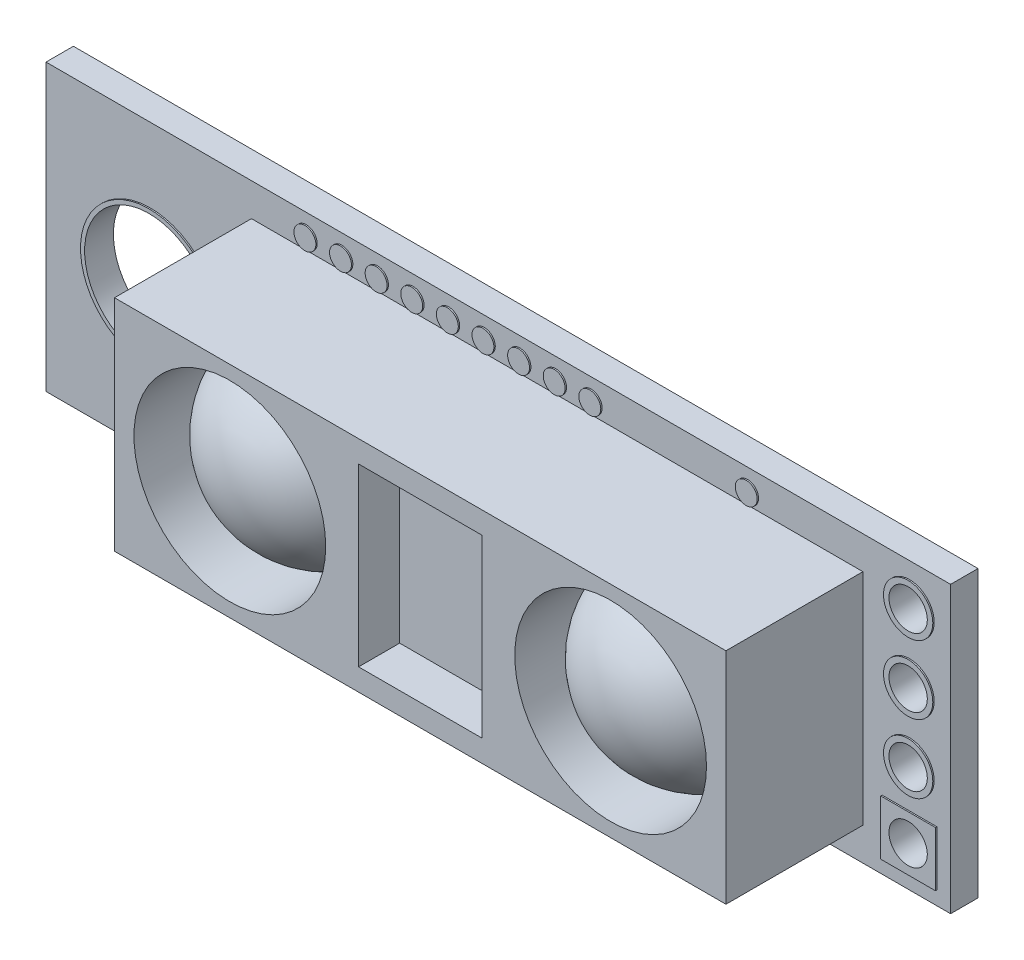
SolidWorks part; units mm, degrees
ref_plane "Alzado" through (0, 0, 0) normal (0, 0, 1) x (1, 0, 0)
ref_plane "Planta" through (0, 0, 0) normal (0, 1, 0) x (1, 0, 0)
ref_plane "Vista lateral" through (0, 0, 0) normal (1, 0, 0) x (0, 0, -1)
sketch "Croquis1" plane through (0, 0, 0) normal (0, 0, 1) x (1, 0, 0)
  line L0 (0, -55) -> (0, 55) construction
  line L1 (-16.51, 5.207) -> (16.51, 5.207)
  line L2 (-16.51, 5.207) -> (-16.51, -5.207)
  line L3 (-16.51, -5.207) -> (16.51, -5.207)
  line L4 (16.51, 5.207) -> (16.51, -5.207)
  line L5 (55, 0) -> (-55, 0) construction
  point P4 (-16.51, 0)
  point P5 (0, 5.207)
  dimension "D1" = 33.02
  dimension "D2" = 10.414
extrude "Saliente-Extruir1" add sketch "Croquis1" along normal mid plane 1
sketch "Croquis2" plane through (0, 0, 0.5) normal (0, 0, 1) x (1, 0, 0)
  line L0 (16.51, -5.207) -> (16.51, 5.207) construction
  line L1 (0.55, 0) -> (-0.55, 0) construction
  line L3 (16.51, 5.207) -> (-16.51, 5.207) construction
  line L5 (14.01, -2.707) -> (16.01, -2.707)
  line L6 (14.01, -2.707) -> (14.01, -4.707)
  line L7 (14.01, -4.707) -> (16.01, -4.707)
  line L8 (16.01, -2.707) -> (16.01, -4.707)
  line L10 (-16.51, -5.207) -> (16.51, -5.207) construction
  circle A0 centre (-12.7, 0) radius 2.5
  circle A1 centre (-12.7, 0) radius 2.35
  circle A2 centre (15.01, 3.707) radius 0.9
  circle A3 centre (15.01, 1.207) radius 0.9
  circle A4 centre (15.01, -1.293) radius 0.9
  circle A5 centre (15.01, 3.707) radius 0.7
  circle A6 centre (15.01, 1.207) radius 0.7
  circle A7 centre (15.01, -1.293) radius 0.7
  point P22 (16.01, -3.707)
  dimension "D2" = 5
  dimension "D3" = 4.7
  dimension "D6" = 1.8
  dimension "D7" = 1.8
  dimension "D8" = 1.8
  dimension "D13" = 1.4
  dimension "D14" = 1.4
  dimension "D15" = 1.4
  dimension "D1" = 29.21
  dimension "D4" = 1.5
  dimension "D5" = 1.5
  dimension "D9" = 2.5
  dimension "D10" = 2.5
  dimension "D11" = 1.5
  dimension "D12" = 1.5
  dimension "D16" = 2
  dimension "D17" = 2
  dimension "D18" = 1.5
  dimension "D19" = 0.5
extrude "Saliente-Extruir2" add sketch "Croquis2" along normal blind 0.05
sketch "Croquis3" plane through (0, 0, 0.5) normal (0, 0, 1) x (1, 0, 0)
  circle A0 centre (-12.7, 0) radius 2.35
  circle A1 centre (15.01, 3.707) radius 0.7
  circle A2 centre (15.01, 1.207) radius 0.7
  circle A3 centre (15.01, -1.293) radius 0.7
extrude "Cortar-Extruir1" cut sketch "Croquis3" against normal blind 30.1
sketch "Croquis4" plane through (0, 0, 0.55) normal (0, 0, 1) x (1, 0, 0)
  circle A0 centre (15.01, -3.707) radius 0.7
  point P0 (15.01, -3.707)
  dimension "D1" = 1.4
extrude "Cortar-Extruir2" cut sketch "Croquis4" against normal blind 40.1
sketch "Croquis5" plane through (0, 0, 0.5) normal (0, 0, 1) x (1, 0, 0)
  line L0 (-16.51, 5.207) -> (-16.51, -5.207) construction
  line L1 (-9.01, 4.007) -> (13.31, 4.007)
  line L2 (-9.01, 4.007) -> (-9.01, -4.007)
  line L3 (-9.01, -4.007) -> (13.31, -4.007)
  line L4 (13.31, 4.007) -> (13.31, -4.007)
  line L5 (16.51, -5.207) -> (16.51, 5.207) construction
  line L6 (16.51, 5.207) -> (-16.51, 5.207) construction
  line L7 (-16.51, -5.207) -> (16.51, -5.207) construction
  dimension "D1" = 7.5
  dimension "D2" = 3.2
  dimension "D3" = 1.2
  dimension "D4" = 1.2
extrude "Saliente-Extruir3" add sketch "Croquis5" along normal blind 5
sketch "Croquis6" plane through (0, 0, 5.5) normal (0, 0, 1) x (1, 0, 0)
  line L0 (-9.01, 0) -> (13.31, 0) construction
  line L1 (-9.01, 4.007) -> (-9.01, -4.007) construction
  line L2 (13.31, -4.007) -> (13.31, 4.007) construction
  line L3 (2.15, 4.007) -> (2.15, -4.007) construction
  line L4 (13.31, 4.007) -> (-9.01, 4.007) construction
  line L5 (-9.01, -4.007) -> (13.31, -4.007) construction
  line L6 (13.31, 4.007) -> (-9.01, 4.007) construction
  line L7 (-0.1, 3.207) -> (4.4, 3.207)
  line L8 (-0.1, 3.207) -> (-0.1, -3.207)
  line L9 (-0.1, -3.207) -> (4.4, -3.207)
  line L10 (4.4, 3.207) -> (4.4, -3.207)
  point P18 (2.15, -3.207)
  dimension "D1" = 4.5
  dimension "D2" = 0.8
  dimension "D3" = 0.8
extrude "Cortar-Extruir3" cut sketch "Croquis6" against normal blind 1.5
sketch "Croquis7" plane through (0, 0, 5.5) normal (0, 0, 1) x (1, 0, 0)
  line L0 (3.3, 0) -> (-3.3, 0) construction
  line L1 (-0.1, 3.207) -> (-0.1, -3.207) construction
  line L2 (4.4, -3.207) -> (4.4, 3.207) construction
  circle A0 centre (-4.8, 0) radius 3.5
  circle A1 centre (9.1, 0) radius 3.5
  dimension "D3" = 7
  dimension "D4" = 7
  dimension "D1" = 4.7
  dimension "D2" = 4.7
extrude "Cortar-Extruir4" cut sketch "Croquis7" against normal blind 3
dome "Cúpula1" faces to dome 1 distance 3 reverse direction no elliptical dome no face at (-1.3, 0, 2.5) parameters "D1"=3
dome "Cúpula2" faces to dome 1 distance 3.2 reverse direction no elliptical dome no face at (12.6, 0, 2.5) parameters "D1"=3.2
sketch "Croquis8" plane through (0, 0, 0.5) normal (0, 0, 1) x (1, 0, 0)
  line L0 (9.1, 0) -> (9.1, 5.8022) construction
  line L1 (13.31, 4.007) -> (-9.01, 4.007) construction
  line L2 (9.1, 4.417) -> (-9.0177, 4.417) construction
  line L3 (-9.01, 4.007) -> (-9.01, -4.007) construction
  line L4 (-9.0177, -4.417) -> (9.8748, -4.417) construction
  line L5 (-9.01, -4.007) -> (13.31, -4.007) construction
  line L6 (9.1, 0) -> (9.1, -4.7092) construction
  circle A0 centre (9.1, 4.417) radius 0.4
  circle A1 centre (-7.01, 4.417) radius 0.4
  circle A2 centre (-5.71, 4.417) radius 0.4
  circle A3 centre (-4.41, 4.417) radius 0.4
  circle A4 centre (-3.11, 4.417) radius 0.4
  circle A5 centre (-1.81, 4.417) radius 0.4
  circle A6 centre (-0.51, 4.417) radius 0.4
  circle A7 centre (0.79, 4.417) radius 0.4
  circle A8 centre (2.09, 4.417) radius 0.4
  circle A9 centre (3.39, 4.417) radius 0.4
  circle A10 centre (-7.01, -4.417) radius 0.4
  circle A11 centre (-5.71, -4.417) radius 0.4
  circle A12 centre (-4.41, -4.417) radius 0.4
  circle A13 centre (-3.11, -4.417) radius 0.4
  circle A14 centre (-1.81, -4.417) radius 0.4
  circle A15 centre (-0.51, -4.417) radius 0.4
  circle A16 centre (0.79, -4.417) radius 0.4
  circle A17 centre (2.09, -4.417) radius 0.4
  circle A18 centre (3.39, -4.417) radius 0.4
  circle A19 centre (9.1, -4.417) radius 0.4
  dimension "D1" = 0.8
  dimension "D3" = 0.8
  dimension "D4" = 0.8
  dimension "D5" = 0.8
  dimension "D6" = 0.8
  dimension "D7" = 0.8
  dimension "D8" = 0.8
  dimension "D9" = 0.8
  dimension "D10" = 0.8
  dimension "D11" = 0.8
  dimension "D22" = 0.8
  dimension "D23" = 0.8
  dimension "D24" = 0.8
  dimension "D25" = 0.8
  dimension "D26" = 0.8
  dimension "D27" = 0.8
  dimension "D28" = 0.8
  dimension "D29" = 0.8
  dimension "D30" = 0.8
  dimension "D31" = 0.8
  dimension "D2" = 0.41
  dimension "D12" = 2
  dimension "D13" = 1.3
  dimension "D14" = 1.3
  dimension "D15" = 1.3
  dimension "D16" = 1.3
  dimension "D17" = 1.3
  dimension "D18" = 1.3
  dimension "D19" = 1.3
  dimension "D20" = 1.3
  dimension "D21" = 0.41
extrude "Saliente-Extruir4" add sketch "Croquis8" along normal blind 0.05
